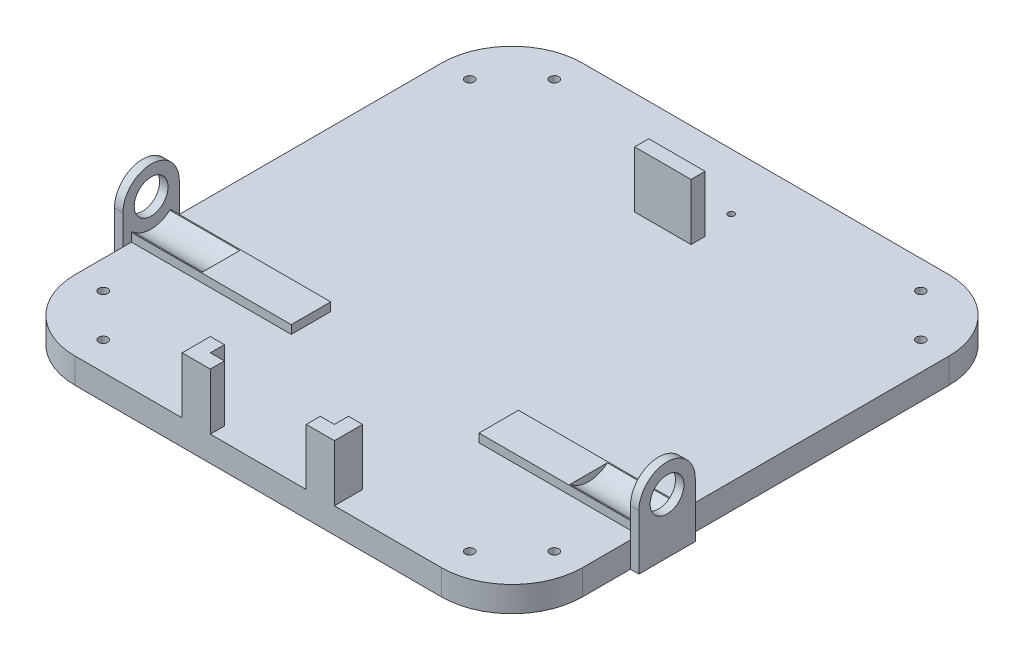
SolidWorks part; units mm, degrees
ref_plane "Front Plane" through (0, 0, 0) normal (0, 0, 1) x (1, 0, 0)
ref_plane "Top Plane" through (0, 0, 0) normal (0, 1, 0) x (1, 0, 0)
ref_plane "Right Plane" through (0, 0, 0) normal (1, 0, 0) x (0, 0, -1)
sketch "Sketch1" plane through (0, 0, 0) normal (0, 1, 0) x (1, 0, 0)
  line L1 (-65, -90) -> (65, -90)
  line L2 (-90, -65) -> (-90, 65)
  line L3 (-65, 90) -> (65, 90)
  line L4 (90, -65) -> (90, 65)
  arc A0 (-90, 65) -> (-65, 90) centre (-65, 65) cw
  arc A1 (65, 90) -> (90, 65) centre (65, 65) cw
  arc A2 (90, -65) -> (65, -90) centre (65, -65) cw
  arc A3 (-65, -90) -> (-90, -65) centre (-65, -65) cw
  point P4 (-90, 0)
  point P6 (0, 90)
  dimension "D3" = 25
  dimension "D1" = 180
  dimension "D2" = 180
extrude "Plate" add sketch "Sketch1" along normal blind 9
sketch "Sketch2" plane through (0, 9, 0) normal (0, 1, 0) x (1, 0, 0)
  line L0 (-7.747, 70) -> (7.747, 70) construction
  line L1 (0, 90) -> (0, 70) construction
  line L2 (-65, 90) -> (65, 90) construction
  circle A1 centre (-7.747, 70) radius 1.09
  circle A2 centre (7.747, 70) radius 1.09
  dimension "D3" = 2.18
  dimension "D1" = 15.494
  dimension "D2" = 20
extrude "Caster Holes" cut sketch "Sketch2" against normal through all
sketch "Sketch3" plane through (0, 9, 0) normal (0, 1, 0) x (1, 0, 0)
  line L0 (-65, 90) -> (-65, -90) construction
  line L1 (65, 90) -> (65, -90) construction
  line L2 (-90, 65) -> (90, 65) construction
  line L3 (-90, -65) -> (90, -65) construction
  circle A0 centre (-65, 80) radius 1.6
  circle A1 centre (-80, 65) radius 1.6
  circle A2 centre (80, 65) radius 1.6
  circle A3 centre (80, -65) radius 1.6
  circle A4 centre (65, 80) radius 1.6
  circle A5 centre (65, -80) radius 1.6
  circle A6 centre (-65, -80) radius 1.6
  circle A7 centre (-80, -65) radius 1.6
  dimension "D1" = 3.2
  dimension "D2" = 15
  dimension "D3" = 15
  dimension "D4" = 15
  dimension "D5" = 15
  dimension "D6" = 15
  dimension "D7" = 15
  dimension "D8" = 15
  dimension "D9" = 15
extrude "Hex Holes" cut sketch "Sketch3" against normal through all
sketch "Sketch4" plane through (0, 9, 0) normal (0, 1, 0) x (1, 0, 0)
  line L0 (-27, -90) -> (-27, -80)
  line L1 (-65, -90) -> (65, -90) construction
  line L2 (-27, -80) -> (-22, -80)
  line L3 (-22, -80) -> (-22, -85)
  line L4 (-22, -85) -> (-17, -85)
  line L5 (-17, -85) -> (-17, -90)
  line L6 (-17, -90) -> (-27, -90)
  line L7 (17, -90) -> (17, -85)
  line L8 (17, -85) -> (22, -85)
  line L9 (22, -85) -> (22, -80)
  line L10 (22, -80) -> (27, -80)
  line L11 (27, -80) -> (27, -90)
  line L12 (27, -90) -> (17, -90)
  line L13 (-10, 58.5) -> (10, 58.5)
  line L14 (10, 58.5) -> (10, 53.5)
  line L15 (10, 53.5) -> (-10, 53.5)
  line L16 (-10, 53.5) -> (-10, 58.5)
  line L17 (-90, -65) -> (-90, 65) construction
  point P20 (0, 53.5)
  dimension "D1" = 5
  dimension "D2" = 44
  dimension "D3" = 63
  dimension "D4" = 20
  dimension "D5" = 5
  dimension "D6" = 138.5
extrude "Battery Holder" add sketch "Sketch4" along normal blind 20
sketch "Sketch5" plane through (0, 9, 0) normal (0, 1, 0) x (1, 0, 0)
  line L0 (-90, -65) -> (-90, 65) construction
  line L1 (-90, -45) -> (-33.3, -45)
  line L2 (-90, -45) -> (-90, -31)
  line L3 (-90, -31) -> (-33.3, -31)
  line L4 (-33.3, -45) -> (-33.3, -31)
  line L5 (90, -65) -> (90, 65) construction
  line L6 (90, -45) -> (33.3, -45)
  line L7 (90, -45) -> (90, -31)
  line L8 (90, -31) -> (33.3, -31)
  line L9 (33.3, -45) -> (33.3, -31)
  line L10 (-65, -90) -> (65, -90) construction
  dimension "D1" = 14
  dimension "D2" = 45
  dimension "D3" = 56.7
extrude "Boss-Extrude2" add sketch "Sketch5" along normal blind 3
sketch "Sketch6" plane through (-90, 0, 0) normal (-1, 0, 0) x (0, 0, 1)
  line L0 (31, 12) -> (45, 12) construction
  line L1 (45, 9) -> (65, 9) construction
  circle A0 centre (38, 19.5) radius 10
  point P5 (38, 12)
  dimension "D1" = 20
  dimension "D2" = 10.5
extrude "Cut-Extrude1" cut sketch "Sketch6" against normal blind 24.8
sketch "Sketch7" plane through (90, 0, 0) normal (1, 0, 0) x (0, 0, -1)
  line L0 (-31, 9) -> (65, 9) construction
  line L1 (-45, 12) -> (-31, 12) construction
  circle A0 centre (-38, 19.5) radius 10
  point P6 (-38, 12)
  dimension "D1" = 20
  dimension "D2" = 10.5
extrude "Cut-Extrude2" cut sketch "Sketch7" against normal blind 24.8
sketch "Sketch8" plane through (90, 0, 0) normal (1, 0, 0) x (0, 0, -1)
  line L0 (-48, 19.5) -> (-48, 0)
  line L1 (-65, 0) -> (65, 0) construction
  line L2 (-48, 0) -> (-28, 0)
  line L3 (-28, 19.5) -> (-28, 0)
  arc A2 (-28, 19.5) -> (-48, 19.5) centre (-38, 19.5) ccw
  circle A3 centre (-38, 19.5) radius 6
  dimension "D1" = 12
  dimension "D2" = 10
  dimension "D3" = 20
extrude "Boss-Extrude4" add sketch "Sketch8" along normal blind 3
sketch "Sketch9" plane through (-90, 0, 0) normal (-1, 0, 0) x (0, 0, 1)
  line L0 (28, 19.5) -> (28, 0)
  line L1 (65, 0) -> (-65, 0) construction
  line L2 (28, 0) -> (48, 0)
  line L3 (48, 0) -> (48, 19.5)
  circle A0 centre (38, 19.5) radius 6
  arc A1 (48, 19.5) -> (28, 19.5) centre (38, 19.5) ccw
  dimension "D1" = 12
extrude "Boss-Extrude5" add sketch "Sketch9" along normal blind 3
